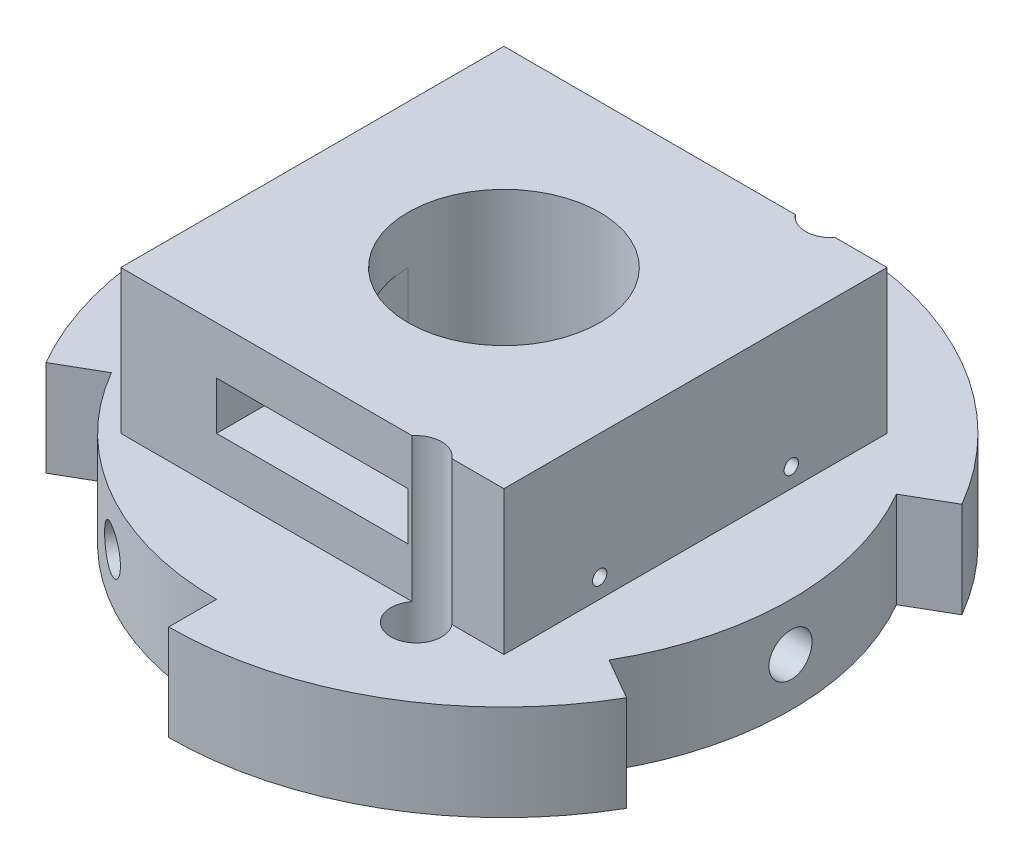
SolidWorks part; units mm, degrees
ref_plane "Front Plane" through (0, 0, 0) normal (0, 0, 1) x (1, 0, 0)
ref_plane "Top Plane" through (0, 0, 0) normal (0, 1, 0) x (1, 0, 0)
ref_plane "Right Plane" through (0, 0, 0) normal (1, 0, 0) x (0, 0, -1)
sketch "Sketch1" plane through (0, 0, 0) normal (0, 1, 0) x (1, 0, 0)
  line L0 (-30.3109, 17.5) -> (-25.9808, 15)
  line L1 (-30.3109, -17.5) -> (-25.9808, -15)
  line L2 (-30.3109, 17.5) -> (0, 0) construction
  line L3 (0, 0) -> (-30.3109, -17.5) construction
  line L4 (-0.4058, 0) -> (-50000.4058, 0) construction
  line L5 (30.3109, 17.5) -> (25.9808, 15)
  line L6 (0, 35) -> (0, 30)
  line L7 (0, -35) -> (0, -30)
  line L8 (30.3109, -17.5) -> (25.9808, -15)
  arc A1 (-30.3109, 17.5) -> (-30.3109, -17.5) centre (0, 0) ccw
  arc A3 (30.3109, 17.5) -> (0, 35) centre (0, 0) ccw
  circle A4 centre (0, 0) radius 30
  arc A5 (0, -35) -> (30.3109, -17.5) centre (0, 0) ccw
  point P5 (-35, 0)
  point P23 (0, 0)
  dimension "D1" = 35
  dimension "D5" = 60
  dimension "D2" = 5
  dimension "D3" = 60
  dimension "D4" = 3
extrude "Boss-Extrude3" add sketch "Sketch1" along normal blind 10 contours A4 L0 A1 L1 | A4 | A4 L5 A3 L6 | L7 A5 L8 A4 region at (-31.0964, 0, 0) region at (0, 0, 0) region at (15.5482, 0, -26.9303) region at (15.5482, 0, 26.9303)
ref_plane "Plane1" through (40, 0, 0) normal (1, 0, 0) x (0, 0, -1)
sketch "Sketch2" plane through (40, 0, 0) normal (1, 0, 0) x (0, 0, -1)
  line L0 (-15, 10) -> (15, 0) construction
  line L1 (15, 10) -> (-15, 0) construction
  circle A0 centre (0, 5) radius 2.25
  dimension "D1" = 4.5
extrude "Cut-Extrude1" cut sketch "Sketch2" against normal blind 25
pattern_circular "CirPattern1" count 3 over 360 about axis through (0, 10, 0) along (0, -1, 0) of "Cut-Extrude1"
sketch "Sketch3" plane through (0, 10, 0) normal (0, 1, 0) x (1, 0, 0)
  line L1 (20, -20) -> (-20, -20)
  line L2 (20, -20) -> (20, 20)
  line L3 (20, 20) -> (-20, 20)
  line L4 (-20, -20) -> (-20, 20)
  line L5 (20, -20) -> (-20, 20) construction
  line L6 (20, 20) -> (-20, -20) construction
  point P0 (0, 0)
  dimension "D1" = 40
  dimension "D2" = 40
extrude "Boss-Extrude4" add sketch "Sketch3" along normal blind 15
sketch "Sketch4" plane through (20, 0, 0) normal (1, 0, 0) x (0, 0, -1)
  line L0 (0, 25) -> (0, 10) construction
  line L1 (-20, 25) -> (20, 25) construction
  line L2 (-20, 10) -> (20, 10) construction
  line L3 (10, 10) -> (10, 12) construction
  line L4 (10, 10) -> (20, 10) construction
  line L7 (-10, 25) -> (-10, 12) construction
  line L8 (10, 25) -> (10, 20.4538) construction
  circle A0 centre (-10, 12) radius 0.75
  circle A1 centre (10, 12) radius 0.75
  point P11 (-10, 18.5)
  dimension "D1" = 1.5
  dimension "D2" = 1.5
  dimension "D3" = 10
  dimension "D4" = 20
  dimension "D5" = 13
  dimension "D6" = 2
sketch "Sketch5" plane through (0, 25, 0) normal (0, 1, 0) x (1, 0, 0)
  circle A0 centre (0, 0) radius 10
  dimension "D1" = 20
extrude "Cut-Extrude5" cut sketch "Sketch5" against normal up to surface (25 mm away) up to face at (0, 0, 0)
extrude "Cut-Extrude6" cut sketch "Sketch4" against normal blind 6 contours A0 | A1
sketch "Sketch7" plane through (-20, 0, 0) normal (-1, 0, 0) x (0, 0, 1)
  line L0 (20, 25) -> (20, 10) construction
  line L1 (-20, 25) -> (20, 25) construction
  circle A0 centre (0, 13) radius 0.75
  dimension "D1" = 1.5
  dimension "D2" = 20
  dimension "D3" = 12
extrude "Cut-Extrude7" cut sketch "Sketch7" against normal blind 6
sketch "Sketch8" plane through (0, 10, 0) normal (0, 1, 0) x (1, 0, 0)
  line L0 (17.5, -30.3109) -> (12.5, -21.6506) construction
  circle A0 centre (0, 0) radius 25 construction
  arc A1 (0, -35) -> (30.3109, -17.5) centre (0, 0) ccw construction
  circle A2 centre (12.5, -21.6506) radius 2.65
  circle A3 centre (-25, 0) radius 2.65
  circle A4 centre (12.5, 21.6506) radius 2.65
  point P16 (0, 0)
  dimension "D1" = 50
  dimension "D2" = 5.3
  dimension "D4" = 25
  dimension "D5" = 25
  dimension "D3" = 3
extrude "Cut-Extrude8" cut sketch "Sketch8" against normal up to surface and the other way up to surface up to face at (0, 0, 10) other way up to face at (0, 25, 10)
sketch "Sketch9" plane through (0, 0, 20) normal (0, 0, 1) x (1, 0, 0)
  line L0 (-20, 25) -> (20, 25) construction
  line L1 (0, 25) -> (0, 17.5) construction
  line L3 (-10, 15) -> (10, 15)
  line L4 (-10, 15) -> (-10, 20)
  line L5 (-10, 20) -> (10, 20)
  line L6 (10, 15) -> (10, 20)
  line L7 (-10, 15) -> (10, 20) construction
  line L8 (-10, 20) -> (10, 15) construction
  dimension "D1" = 7.5
  dimension "D2" = 20
  dimension "D3" = 5
extrude "Cut-Extrude9" cut sketch "Sketch9" against normal up to surface (20 mm away) up to plane "Front Plane"
